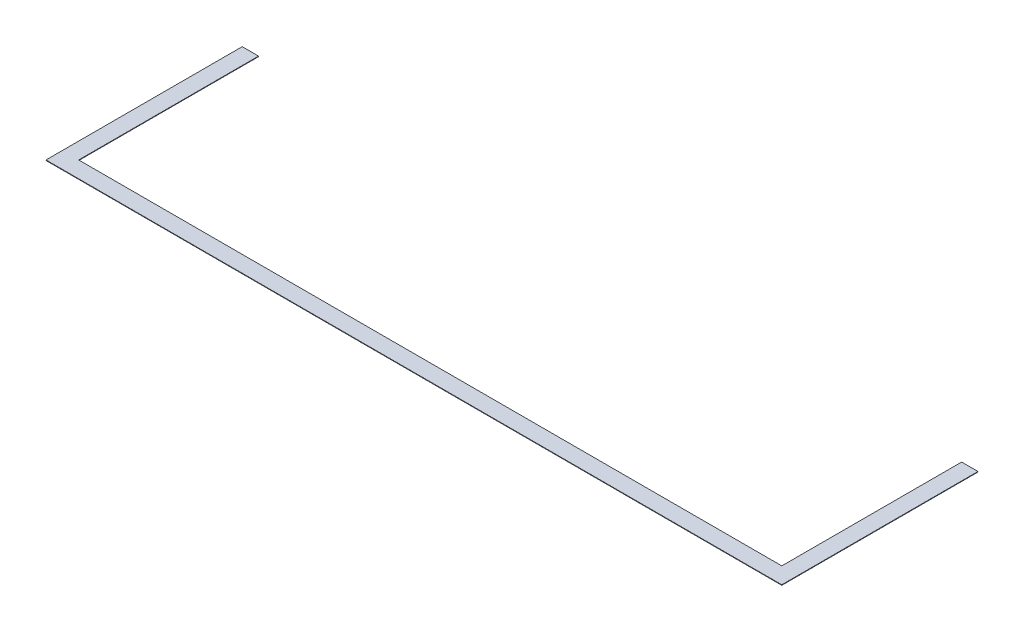
SolidWorks part; units mm, degrees
ref_plane "Front Plane" through (0, 0, 0) normal (0, 0, 1) x (1, 0, 0)
ref_plane "Top Plane" through (0, 0, 0) normal (0, 1, 0) x (1, 0, 0)
ref_plane "Right Plane" through (0, 0, 0) normal (1, 0, 0) x (0, 0, -1)
sketch "Sketch1" plane through (0, 0, 0) normal (0, 1, 0) x (1, 0, 0)
  line L0 (0, 0) -> (0, -609.6)
  line L1 (0, -609.6) -> (2286, -609.6)
  line L2 (2286, -609.6) -> (2286, 0)
  line L3 (2286, 0) -> (2235.2, 0)
  line L4 (2235.2, 0) -> (2235.2, -558.8)
  line L5 (2235.2, -558.8) -> (50.8, -558.8)
  line L6 (50.8, -558.8) -> (50.8, 0)
  line L7 (50.8, 0) -> (0, 0)
  line L8 (50.8, -558.8) -> (50.8, -609.6) construction
  dimension "D1" = 50.8
  dimension "D2" = 2286
  dimension "D3" = 609.6
extrude "Boss-Extrude1" add sketch "Sketch1" along normal blind 1.5875 contours L8 L6 L7 L0 L1 | L5 L8 L1 L2 L3 L4 | L7 L0 L1 L2 L3 L4 L5 L6 region at (25.4, 0, 304.8) region at (73.9684, 0, 584.2)
